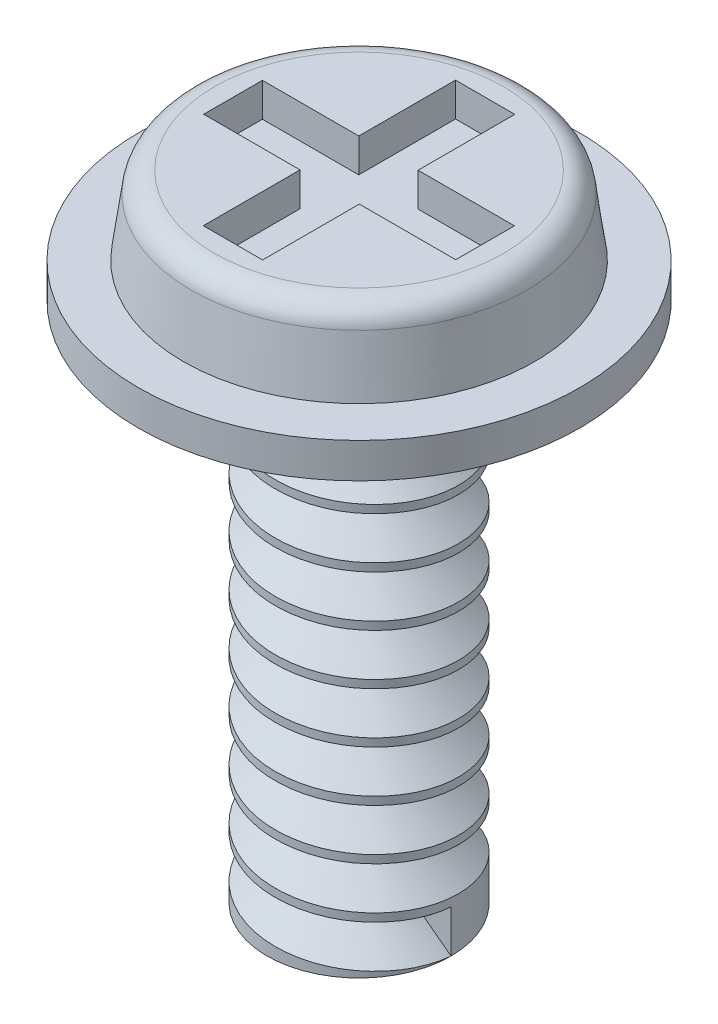
SolidWorks part; units mm, degrees
ref_plane "Front Plane" through (0, 0, 0) normal (0, 0, 1) x (1, 0, 0)
ref_plane "Top Plane" through (0, 0, 0) normal (0, 1, 0) x (1, 0, 0)
ref_plane "Right Plane" through (0, 0, 0) normal (1, 0, 0) x (0, 0, -1)
sketch "Sketch1" plane through (0, 0, 0) normal (0, 1, 0) x (1, 0, 0)
  circle A0 centre (0, 0) radius 1.365
  dimension "D1" = 2.73
extrude "Boss-Extrude1" add sketch "Sketch1" along normal blind 7.74
sketch "Sketch2" plane through (0, 7.74, 0) normal (0, 1, 0) x (1, 0, 0)
  circle A0 centre (0, 0) radius 3.275
  dimension "D1" = 6.55
extrude "Boss-Extrude2" add sketch "Sketch2" along normal blind 0.52
sketch "Sketch3" plane through (0, 8.26, 0) normal (0, 1, 0) x (1, 0, 0)
  circle A0 centre (0, 0) radius 2.6064
extrude "Boss-Extrude3" add sketch "Sketch3" along normal blind 1.16
sketch "Sketch4" plane through (0, 0, 0) normal (0, 0, 1) x (1, 0, 0)
  line L0 (-2.6064, 8.26) -> (-2.4892, 9.1193)
  line L1 (-2.1446, 9.42) -> (0, 9.42) construction
  line L2 (2.6064, 9.42) -> (-2.6064, 9.42) construction
  line L3 (-2.6064, 8.26) -> (-2.6064, 9.5049)
  line L4 (-2.6064, 9.5049) -> (-2.1446, 9.5049)
  line L5 (-2.1446, 9.5049) -> (-2.1446, 9.42)
  line L6 (0, 10.1136) -> (0, -0.9689) construction
  line L7 (0, -3.6025) -> (0, 3.6025) construction
  arc A0 (-2.4892, 9.1193) -> (-2.1446, 9.42) centre (-2.1446, 9.0723) cw
revolve "Cut-Revolve1" cut sketch "Sketch4" angle 360 about L6
sketch "Sketch5" plane through (0, 9.42, 0) normal (0, 1, 0) x (1, 0, 0)
  line L0 (-0.44, 1.8715) -> (0.44, 1.8715)
  line L1 (0, -3.6025) -> (0, 3.6025) construction
  line L2 (0.44, 1.8715) -> (0.44, 0.4356)
  line L3 (0.44, 0.4356) -> (1.87, 0.4356)
  line L4 (-0.44, -1.8715) -> (0.44, -1.8715)
  line L5 (1.87, 0.4356) -> (1.87, -0.4356)
  line L6 (-3.6025, 0) -> (3.6025, 0) construction
  line L7 (0.44, -0.4356) -> (1.87, -0.4356)
  line L8 (0.44, -1.8715) -> (0.44, -0.4356)
  line L9 (-0.44, -1.8715) -> (-0.44, -0.4356)
  line L10 (-0.44, -0.4356) -> (-1.87, -0.4356)
  line L11 (-1.87, 0.4356) -> (-1.87, -0.4356)
  line L12 (-0.44, 0.4356) -> (-1.87, 0.4356)
  line L13 (-0.44, 1.8715) -> (-0.44, 0.4356)
  point P12 (1.87, 0)
  point P14 (0, -1.8715)
  point P19 (0, 1.8715)
  dimension "D1" = 0.4356
  dimension "D2" = 0.44
  dimension "D3" = 1.8715
  dimension "D4" = 1.87
extrude "Cut-Extrude1" cut sketch "Sketch5" against normal blind 0.5
sketch "Sketch6" plane through (0, 0, 0) normal (0, 0, 1) x (1, 0, 0)
  line L0 (1.365, 0.6309) -> (0.9242, 0.3327)
  line L1 (1.365, 0) -> (1.365, 7.74) construction
  line L2 (0.9242, 0.3327) -> (1.365, 0)
  line L3 (3.6025, 0) -> (-3.6025, 0) construction
  line L4 (1.365, 0.6309) -> (1.365, 0)
  dimension "D1" = 0.5323
sketch "Sketch7" plane through (0, 0, 0) normal (0, 1, 0) x (1, 0, 0)
  circle A0 centre (0, 0) radius 1.365
  dimension "D1" = 2.73
curve "Helix/Spiral1" pitch 0.75 height 7.6875 turns 10.25
sweep "Cut-Sweep1" cut profiles "Sketch6" path "Helix/Spiral1"
